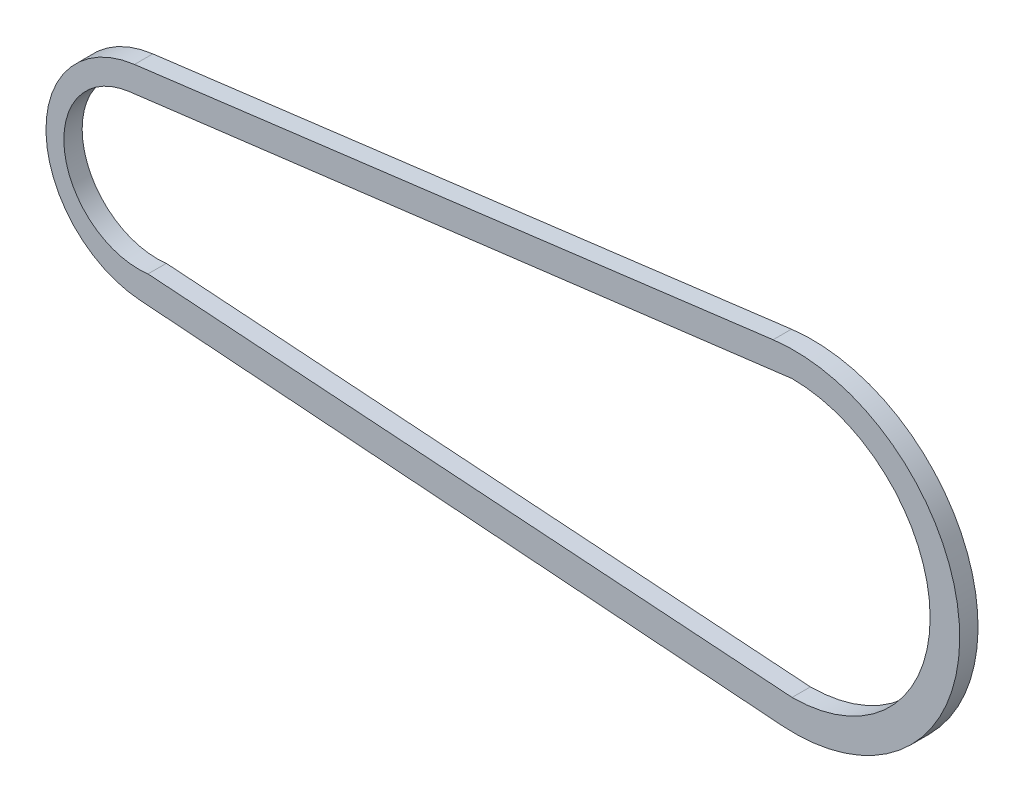
SolidWorks part; units mm, degrees
ref_plane "前视基准面" through (0, 0, 0) normal (0, 0, 1) x (1, 0, 0)
ref_plane "上视基准面" through (0, 0, 0) normal (0, 1, 0) x (1, 0, 0)
ref_plane "右视基准面" through (0, 0, 0) normal (1, 0, 0) x (0, 0, -1)
sketch "草图1" plane through (0, 0, 0) normal (0, 0, 1) x (1, 0, 0)
  line L1 (424.6163, 129.3866) -> (424.6163, -70.6134)
  line L2 (424.6163, -70.6134) -> (-74.0256, -33.7861)
  line L3 (-74.0256, -33.7861) -> (-74.0256, 66.2139)
  line L4 (-74.0256, 66.2139) -> (424.6163, 129.3866)
extrude "凸台-拉伸1" add sketch "草图1" along normal blind 10
fillet "圆角1" 2 edges at (-74.0256, 66.2139, 5) (-74.0256, -33.7861, 5) type full round first side face at (175.2953, 97.8002, 5) second side face at (175.2953, -52.1998, 5) middle face at (-74.0256, 16.2139, 5)
fillet "圆角2" 2 edges at (424.6163, -70.6134, 5) (424.6163, 129.3866, 5) type full round first side face at (200.8825, -54.0895, 5) second side face at (199.4454, 100.8598, 5) middle face at (424.6163, 29.3866, 5)
sketch "草图2" plane through (0, 0, 10) normal (0, 0, 1) x (1, 0, 0)
  line L0 (-28.4872, 58.0836) -> (333.137, 103.2867)
  line L1 (-18.3537, -22.9838) -> (333.137, -47.3901)
  arc A0 (-28.4872, 58.0836) -> (-18.3537, -22.9838) centre (-23.4205, 17.5499) ccw
  arc A1 (333.137, 103.2867) -> (333.137, -47.3901) centre (333.137, 27.9483) cw
  point P6 (0, 0)
extrude "切除-拉伸1" cut sketch "草图2" against normal blind 10
